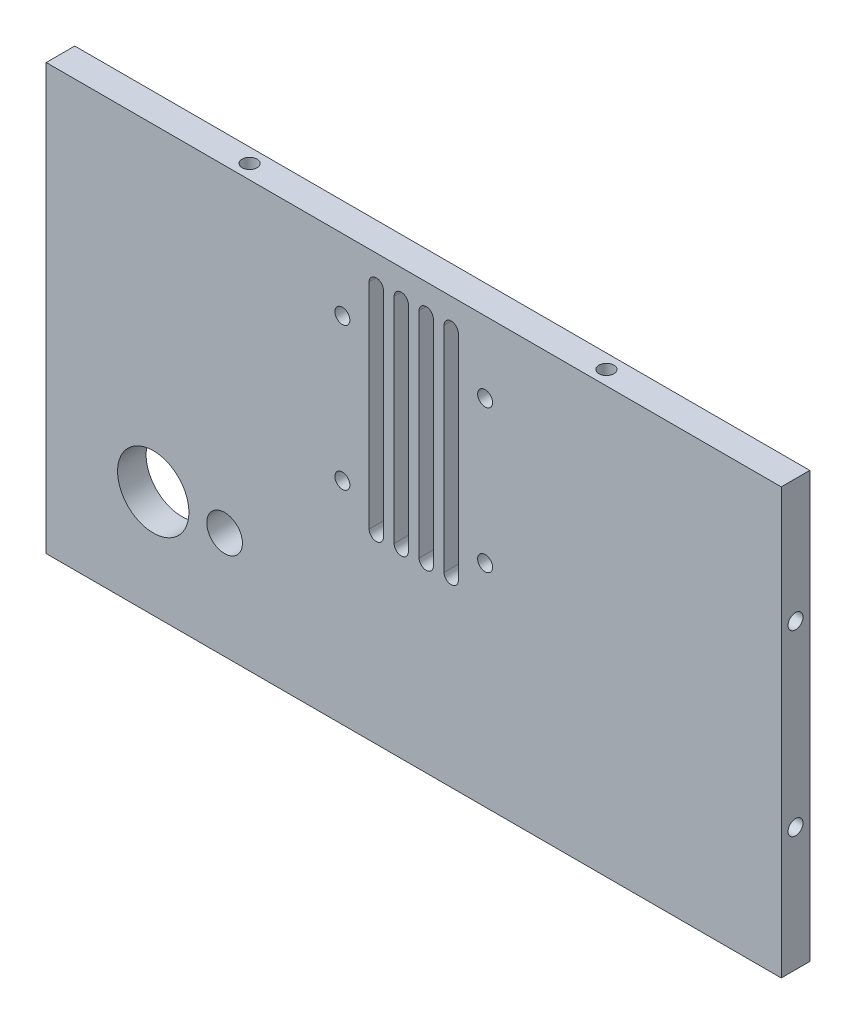
SolidWorks part; units mm, degrees
ref_plane "Front Plane" through (0, 0, 0) normal (1, 0, 0) x (0, 1, 0)
ref_plane "Top Plane" through (0, 0, 0) normal (0, 0, 1) x (0, 1, 0)
ref_plane "Right Plane" through (0, 0, 0) normal (0, 1, 0) x (-1, 0, 0)
sketch "Sketch1" plane through (0, 0, 0) normal (0, 0, 1) x (0, 1, 0)
  line L0 (51.2019, 113.5) -> (111.2019, 113.5) construction
  line L1 (0, 0) -> (119.2019, 0)
  line L2 (0, 0) -> (0, 206)
  line L3 (0, 206) -> (119.2019, 206)
  line L4 (119.2019, 0) -> (119.2019, 206)
  line L5 (51.2019, 115.5) -> (111.2019, 115.5)
  line L6 (51.2019, 111.5) -> (111.2019, 111.5)
  line L7 (51.2019, 106.5) -> (111.2019, 106.5) construction
  line L8 (51.2019, 108.5) -> (111.2019, 108.5)
  line L9 (51.2019, 104.5) -> (111.2019, 104.5)
  line L10 (51.2019, 99.5) -> (111.2019, 99.5) construction
  line L11 (51.2019, 101.5) -> (111.2019, 101.5)
  line L12 (51.2019, 97.5) -> (111.2019, 97.5)
  line L13 (51.2019, 92.5) -> (111.2019, 92.5) construction
  line L14 (51.2019, 94.5) -> (111.2019, 94.5)
  line L15 (51.2019, 90.5) -> (111.2019, 90.5)
  line L16 (6, 200) -> (113.2019, 200) construction
  line L17 (113.2019, 6) -> (113.2019, 200) construction
  line L18 (6, 6) -> (113.2019, 6) construction
  line L19 (6, 6) -> (6, 200) construction
  line L22 (119.2019, 103) -> (0, 103) construction
  arc A0 (51.2019, 115.5) -> (51.2019, 111.5) centre (51.2019, 113.5) ccw
  arc A1 (111.2019, 111.5) -> (111.2019, 115.5) centre (111.2019, 113.5) ccw
  arc A2 (51.2019, 108.5) -> (51.2019, 104.5) centre (51.2019, 106.5) ccw
  arc A3 (111.2019, 104.5) -> (111.2019, 108.5) centre (111.2019, 106.5) ccw
  arc A4 (51.2019, 101.5) -> (51.2019, 97.5) centre (51.2019, 99.5) ccw
  arc A5 (111.2019, 97.5) -> (111.2019, 101.5) centre (111.2019, 99.5) ccw
  arc A6 (51.2019, 94.5) -> (51.2019, 90.5) centre (51.2019, 92.5) ccw
  arc A7 (111.2019, 90.5) -> (111.2019, 94.5) centre (111.2019, 92.5) ccw
  circle A8 centre (59.2019, 123) radius 2.1
  circle A9 centre (99.2019, 123) radius 2.1
  circle A10 centre (59.2019, 83) radius 2.1
  circle A11 centre (99.2019, 83) radius 2.1
  circle A12 centre (30, 176) radius 10
  circle A13 centre (30, 156) radius 5
  point P7 (81.2019, 113.5)
  point P12 (81.2019, 106.5)
  point P19 (81.2019, 99.5)
  point P26 (81.2019, 92.5)
  point P39 (0, 0)
  point P40 (90.1952, 103)
  dimension "D9" = 4.2
  dimension "D13" = 20
  dimension "D14" = 10
  dimension "D1" = 119.2019
  dimension "D2" = 206
  dimension "D4" = 3
  dimension "D5" = 3
  dimension "D7" = 4
  dimension "D8" = 60
  dimension "D11" = 20
  dimension "D12" = 40
  dimension "D10" = 40
  dimension "D6" = 3
  dimension "D15" = 30
  dimension "D16" = 30
  dimension "D17" = 20
  dimension "D3" = 6
extrude "Boss-Extrude1" add sketch "Sketch1" along normal blind 8
sketch "Sketch2" plane through (0, 0, 0) normal (0, -1, 0) x (1, 0, 0)
  line L2 (-206, 4) -> (0, 4) construction
  line L3 (-206, 8) -> (-206, 0) construction
  line L4 (0, 8) -> (0, 0) construction
  line L5 (-103, 8) -> (-103, 0) construction
  line L6 (-206, 8) -> (0, 8) construction
  line L7 (-206, 0) -> (0, 0) construction
  circle A0 centre (-153, 4) radius 2.1
  circle A1 centre (-53, 4) radius 2.1
  point P4 (0, 0)
  point P17 (0, 0)
  dimension "D1" = 4.2
  dimension "D2" = 50
extrude "Cut-Extrude1" cut sketch "Sketch2" against normal blind 14
extrude "Cut-Extrude2" cut sketch "Sketch2<2>" along normal blind 14 from surface starting at face at (-103, 119.2019, 4)
sketch "Sketch2<2>" plane through (0, 0, 0) normal (0, -1, 0) x (1, 0, 0) same geometry as "Sketch2"
sketch "Sketch3" plane through (0, 0, 0) normal (1, 0, 0) x (0, 1, 0)
  line L0 (105.2019, 4) -> (119.2019, 4) construction
  line L1 (0, 4) -> (119.2019, 4) construction
  line L2 (0, 8) -> (0, 0) construction
  line L3 (119.2019, 8) -> (119.2019, 0) construction
  line L4 (0, 8) -> (119.2019, 8) construction
  line L5 (59.6009, 8) -> (59.6009, 0) construction
  line L6 (0, 0) -> (119.2019, 0) construction
  circle A0 centre (34.6009, 4) radius 2.1
  circle A1 centre (84.601, 4) radius 2.1
  point P18 (0, 0)
  point P19 (0, 0)
  point P20 (62.0525, 3)
  point P21 (0, 0)
  dimension "D1" = 4.2
  dimension "D2" = 50
extrude "Cut-Extrude3" cut sketch "Sketch3" against normal blind 14
extrude "Cut-Extrude4" cut sketch "Sketch3<2>" along normal blind 14 from surface starting at face at (-206, 59.6009, 4)
sketch "Sketch3<2>" plane through (0, 0, 0) normal (1, 0, 0) x (0, 1, 0) same geometry as "Sketch3"
sketch "Sketch4" plane through (0, 0, 8) normal (0, 0, 1) x (1, 0, 0)
  line L0 (0, 0) -> (0, 119.2019) construction
  line L1 (-206, 0) -> (0, 0) construction
  line L2 (0, 119.2019) -> (-206, 119.2019) construction
  line L3 (-206, 119.2019) -> (-206, 0) construction
  line L4 (0, 0) -> (0, 119.2019)
  line L5 (-206, 0) -> (0, 0)
  line L6 (0, 119.2019) -> (-206, 119.2019)
  line L7 (-206, 119.2019) -> (-206, 0)
equation "\"MotorDriverLength\"= 60mm"
equation "\"MotorLength\"= 60"
equation "\"MotorDriverWidth\"=44"
equation "\"MotorWidth\"= 37"
equation "\"InnerWallThickness\"=3"
equation "\"BatteryWidth\"= 60"
equation "\"OuterWallThickness\" = 8"
equation "\"CompartmentHeight\"=37"
equation "\"CompartmentWidth\"= \"MotorDriverLength\""
equation "\"MotorDiameter\"=37"
equation "\"BatteryHeight\"=24.2019"
equation "\"MotorDriverHeight\"=28"
equation "\"CircuitHeight\"=30"
equation "\"FanThickness\"= 10"
equation "\"FanHeight\"=50"
equation "\"MotorShaftHole\"=12"
equation "\"BearingBore\"=4"
equation "\"MinShinWidth\"= 20"
equation "\"ShinThickness\"=10"
equation "\"PivotDistance\"=30"
equation "\"ThighLength\"= 200"
equation "\"KneeLength\" =20"
equation "\"HipBore\"=27"
equation "\"ThighThickness\"=20"
equation "\"MaxBending\"=135"
equation "\"MaxStretchingAngle\"= 140"
equation "\"ThighJointDistance\"=157.485"
equation "\"ShinLength\"=120"
equation "\"BearingDiameter\"= 10"
equation "\"CircuitLength\"=50"
equation "\"ChessisInnerWidth\"= \"OuterWallThickness\" * 2 + \"MotorDriverLength\" + \"MotorDiameter\" + \"InnerWallThickness\" * 3 + \"CircuitLength\""
equation "\"ChessisHeight\"= \"BatteryHeight\" + 10 + \"InnerWallThickness\" + \"MotorDriverHeight\"*2 + 10 + \"OuterWallThickness\" * 2"
equation "\"D1@Sketch1\"=\"ChessisHeight\""
equation "\"ChassisWidth\"= \"MotorDriverWidth\"*4+30"
equation "\"D2@Sketch1\"=\"ChassisWidth\""
equation "\"D1@Boss-Extrude1\"=\"OuterWallThickness\""
